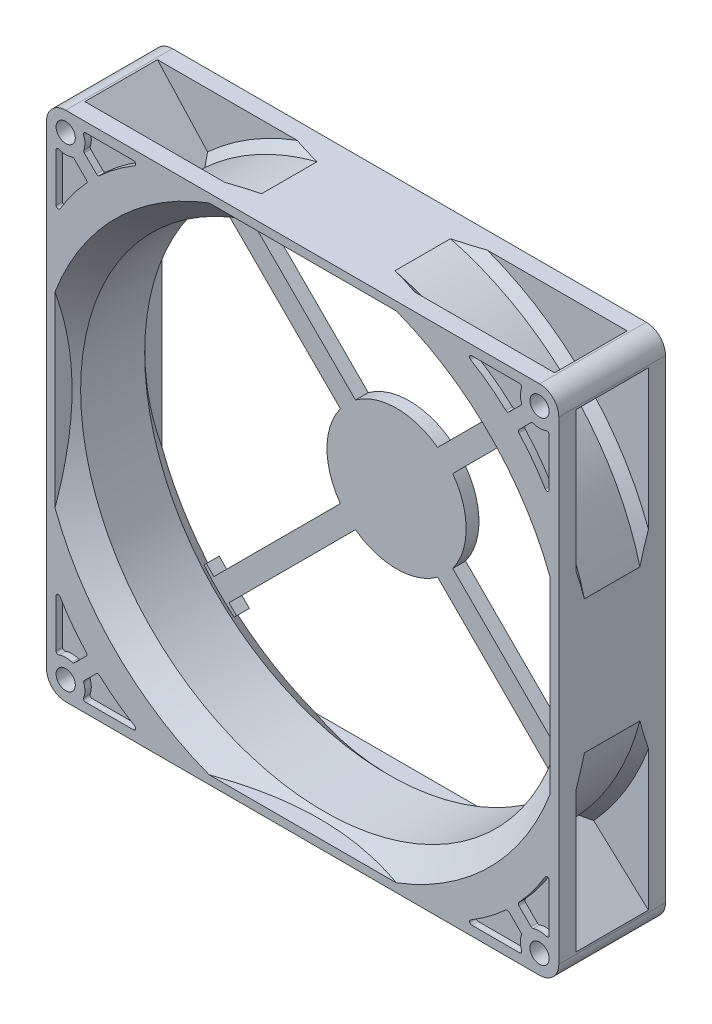
SolidWorks part; units mm, degrees
ref_plane "Front Plane" through (0, 0, 0) normal (0, 0, 1) x (1, 0, 0)
ref_plane "Top Plane" through (0, 0, 0) normal (0, 1, 0) x (1, 0, 0)
ref_plane "Right Plane" through (0, 0, 0) normal (1, 0, 0) x (0, 0, -1)
sketch "Sketch1" plane through (0, 0, 0) normal (0, 0, 1) x (1, 0, 0)
  line L1 (-55.5, -60) -> (55.5, -60)
  line L2 (-60, -55.5) -> (-60, 55.5)
  line L3 (-55.5, 60) -> (55.5, 60)
  line L4 (60, -55.5) -> (60, 55.5)
  line L5 (-60, -60) -> (60, 60) construction
  line L6 (-60, 60) -> (60, -60) construction
  arc A0 (-55.5, -60) -> (-60, -55.5) centre (-55.5, -55.5) cw
  arc A1 (55.5, -60) -> (60, -55.5) centre (55.5, -55.5) ccw
  arc A2 (55.5, 60) -> (60, 55.5) centre (55.5, 55.5) cw
  arc A3 (-60, 55.5) -> (-55.5, 60) centre (-55.5, 55.5) cw
  circle A4 centre (-55.5, 55.5) radius 2.25
  circle A5 centre (-55.5, -55.5) radius 2.25
  circle A6 centre (55.5, -55.5) radius 2.25
  circle A7 centre (55.5, 55.5) radius 2.25
  point P0 (0, 0)
  dimension "D3" = 4.5
  dimension "D4" = 4.5
  dimension "D1" = 120
  dimension "D2" = 120
  dimension "D5" = 4.5
extrude "Boss-Extrude1" add sketch "Sketch1" along normal mid plane 25
sketch "Sketch3" plane through (0, 0, 12.5) normal (0, 0, 1) x (1, 0, 0)
  line L0 (-39.6029, -57.75) -> (-50.8163, -57.75)
  line L1 (-48.3027, -50.6714) -> (-51.1323, -53.5)
  line L2 (-60, 0) -> (60, 0) construction
  line L3 (-60, 55.5) -> (-60, -55.5) construction
  line L4 (60, -55.5) -> (60, 55.5) construction
  line L5 (0, 60) -> (0, -60) construction
  line L6 (55.5, 60) -> (-55.5, 60) construction
  line L7 (-55.5, -60) -> (55.5, -60) construction
  line L8 (-48.3027, 50.6714) -> (-51.1323, 53.5)
  line L9 (-39.6029, 57.75) -> (-50.8163, 57.75)
  line L10 (39.6029, 57.75) -> (50.8163, 57.75)
  line L11 (48.3027, 50.6714) -> (51.1323, 53.5)
  line L12 (48.3027, -50.6714) -> (51.1323, -53.5)
  line L13 (39.6029, -57.75) -> (50.8163, -57.75)
  line L14 (-58.682, 58.682) -> (58.682, -58.682) construction
  line L15 (58.682, 58.682) -> (-58.682, -58.682) construction
  line L16 (-50.6714, -48.3027) -> (-53.5, -51.1323)
  line L17 (-57.75, -39.6029) -> (-57.75, -50.8163)
  line L18 (-50.6714, 48.3027) -> (-53.5, 51.1323)
  line L19 (-57.75, 39.6029) -> (-57.75, 50.8163)
  line L20 (57.75, 39.6029) -> (57.75, 50.8163)
  line L21 (50.6714, 48.3027) -> (53.5, 51.1323)
  line L22 (57.75, -39.6029) -> (57.75, -50.8163)
  line L23 (50.6714, -48.3027) -> (53.5, -51.1323)
  arc A0 (-51.2846, -57.075) -> (-51.2509, -54.0183) centre (-55.5, -55.5) ccw
  arc A1 (-39.6029, -57.75) -> (-39.3478, -56.82) centre (-39.6029, -57.25) ccw
  arc A2 (-39.3478, -56.82) -> (-47.6098, -50.6579) centre (-14.3459, -14.6785) cw
  arc A3 (-47.6098, -50.6579) -> (-48.3027, -50.6714) centre (-47.9492, -51.025) ccw
  arc A4 (-50.8163, -57.75) -> (-51.2846, -57.075) centre (-50.8163, -57.25) cw
  arc A5 (-51.1323, -53.5) -> (-51.2509, -54.0183) centre (-50.7788, -53.8536) ccw
  circle A6 centre (-55.5, -55.5) radius 2.25 construction
  arc A7 (-51.1323, 53.5) -> (-51.2509, 54.0183) centre (-50.7788, 53.8536) cw
  arc A8 (-50.8163, 57.75) -> (-51.2846, 57.075) centre (-50.8163, 57.25) ccw
  arc A9 (-47.6098, 50.6579) -> (-48.3027, 50.6714) centre (-47.9492, 51.025) cw
  arc A10 (-39.3478, 56.82) -> (-47.6098, 50.6579) centre (-14.3459, 14.6785) ccw
  arc A11 (-39.6029, 57.75) -> (-39.3478, 56.82) centre (-39.6029, 57.25) cw
  arc A12 (-51.2846, 57.075) -> (-51.2509, 54.0183) centre (-55.5, 55.5) cw
  arc A13 (51.2846, 57.075) -> (51.2509, 54.0183) centre (55.5, 55.5) ccw
  arc A14 (39.6029, 57.75) -> (39.3478, 56.82) centre (39.6029, 57.25) ccw
  arc A15 (39.3478, 56.82) -> (47.6098, 50.6579) centre (14.3459, 14.6785) cw
  arc A16 (47.6098, 50.6579) -> (48.3027, 50.6714) centre (47.9492, 51.025) ccw
  arc A17 (50.8163, 57.75) -> (51.2846, 57.075) centre (50.8163, 57.25) cw
  arc A18 (51.1323, 53.5) -> (51.2509, 54.0183) centre (50.7788, 53.8536) ccw
  arc A19 (51.1323, -53.5) -> (51.2509, -54.0183) centre (50.7788, -53.8536) cw
  arc A20 (50.8163, -57.75) -> (51.2846, -57.075) centre (50.8163, -57.25) ccw
  arc A21 (47.6098, -50.6579) -> (48.3027, -50.6714) centre (47.9492, -51.025) cw
  arc A22 (39.3478, -56.82) -> (47.6098, -50.6579) centre (14.3459, -14.6785) ccw
  arc A23 (39.6029, -57.75) -> (39.3478, -56.82) centre (39.6029, -57.25) cw
  arc A24 (51.2846, -57.075) -> (51.2509, -54.0183) centre (55.5, -55.5) cw
  arc A25 (-55.5, 60) -> (-60, 55.5) centre (-55.5, 55.5) ccw construction
  arc A26 (55.5, -60) -> (60, -55.5) centre (55.5, -55.5) ccw construction
  arc A27 (60, 55.5) -> (55.5, 60) centre (55.5, 55.5) ccw construction
  arc A28 (-60, -55.5) -> (-55.5, -60) centre (-55.5, -55.5) ccw construction
  arc A29 (-53.5, -51.1323) -> (-54.0183, -51.2509) centre (-53.8536, -50.7788) cw
  arc A30 (-57.75, -50.8163) -> (-57.075, -51.2846) centre (-57.25, -50.8163) ccw
  arc A31 (-57.075, -51.2846) -> (-54.0183, -51.2509) centre (-55.5, -55.5) cw
  arc A32 (-50.6579, -47.6098) -> (-50.6714, -48.3027) centre (-51.025, -47.9492) cw
  arc A33 (-56.82, -39.3478) -> (-50.6579, -47.6098) centre (-14.6785, -14.3459) ccw
  arc A34 (-57.75, -39.6029) -> (-56.82, -39.3478) centre (-57.25, -39.6029) cw
  arc A35 (-57.075, 51.2846) -> (-54.0183, 51.2509) centre (-55.5, 55.5) ccw
  arc A36 (-57.75, 50.8163) -> (-57.075, 51.2846) centre (-57.25, 50.8163) cw
  arc A37 (-53.5, 51.1323) -> (-54.0183, 51.2509) centre (-53.8536, 50.7788) ccw
  arc A38 (-50.6579, 47.6098) -> (-50.6714, 48.3027) centre (-51.025, 47.9492) ccw
  arc A39 (-57.75, 39.6029) -> (-56.82, 39.3478) centre (-57.25, 39.6029) ccw
  arc A40 (-56.82, 39.3478) -> (-50.6579, 47.6098) centre (-14.6785, 14.3459) cw
  arc A41 (57.75, 39.6029) -> (56.82, 39.3478) centre (57.25, 39.6029) cw
  arc A42 (57.75, 50.8163) -> (57.075, 51.2846) centre (57.25, 50.8163) ccw
  arc A43 (50.6579, 47.6098) -> (50.6714, 48.3027) centre (51.025, 47.9492) cw
  arc A44 (56.82, 39.3478) -> (50.6579, 47.6098) centre (14.6785, 14.3459) ccw
  arc A45 (53.5, 51.1323) -> (54.0183, 51.2509) centre (53.8536, 50.7788) cw
  arc A46 (57.075, 51.2846) -> (54.0183, 51.2509) centre (55.5, 55.5) cw
  arc A47 (57.75, -39.6029) -> (56.82, -39.3478) centre (57.25, -39.6029) ccw
  arc A48 (56.82, -39.3478) -> (50.6579, -47.6098) centre (14.6785, -14.3459) cw
  arc A49 (50.6579, -47.6098) -> (50.6714, -48.3027) centre (51.025, -47.9492) ccw
  arc A50 (57.075, -51.2846) -> (54.0183, -51.2509) centre (55.5, -55.5) ccw
  arc A51 (57.75, -50.8163) -> (57.075, -51.2846) centre (57.25, -50.8163) cw
  arc A52 (53.5, -51.1323) -> (54.0183, -51.2509) centre (53.8536, -50.7788) ccw
  point P14 (-51.6029, -57.75)
  point P44 (-51.6029, 57.75)
  point P59 (51.6029, 57.75)
  point P74 (51.6029, -57.75)
  point P97 (-57.75, -51.6029)
  point P111 (-57.75, 51.6029)
  point P125 (57.75, 51.6029)
  point P146 (57.75, -51.6029)
  dimension "D1" = 9
  dimension "D2" = 49
  dimension "D3" = 0.5
  dimension "D5" = 0.5
  dimension "D6" = 0.5
  dimension "D4" = 12
  dimension "D7" = 4.001
  dimension "D8" = 4.25
  dimension "D9" = 2.475
extrude "Cut-Extrude1" cut sketch "Sketch3" against normal blind 1.5
mirror "Mirror1" about plane through (0, 0, 0) normal (0, 0, 1) of "Cut-Extrude1"
sketch "Sketch5" plane through (0, 0, 12.5) normal (0, 0, 1) x (1, 0, 0)
  line L0 (55.5, 60) -> (-55.5, 60) construction
  line L1 (-58, -58) -> (58, -58)
  line L2 (-58, -58) -> (-58, 58)
  line L3 (-58, 58) -> (58, 58)
  line L4 (58, -58) -> (58, 58)
  line L5 (-58, -58) -> (58, 58) construction
  line L6 (-58, 58) -> (58, -58) construction
  line L7 (60, -55.5) -> (60, 55.5) construction
  point P0 (0, 0)
  dimension "D1" = 2
  dimension "D2" = 2
split "Split1" trim tools "Sketch5" bodies to split 103 resulting bodies 104 105
sketch "Sketch6" plane through (0, 0, 12.5) normal (0, 0, 1) x (1, 0, 0)
  circle A0 centre (0, 0) radius 57
  dimension "D1" = 114
extrude "Cut-Extrude2" cut sketch "Sketch6" against normal blind 25
chamfer "Chamfer1" distance 5 angle 45 2 edges at (57, 0, -12.5) (57, 0, 12.5)
sketch "Sketch7" plane through (0, 0, -12.5) normal (0, 0, -1) x (-1, 0, 0)
  line L0 (0, 60) -> (0, -60) construction
  line L1 (-55.5, 60) -> (55.5, 60) construction
  line L2 (55.5, -60) -> (-55.5, -60) construction
  line L3 (-60, 0) -> (60, 0) construction
  line L4 (-60, -55.5) -> (-60, 55.5) construction
  line L5 (60, 55.5) -> (60, -55.5) construction
  circle A0 centre (-55.5, 55.5) radius 3.4
  circle A1 centre (-55.5, -55.5) radius 3.4
  circle A2 centre (55.5, 55.5) radius 3.4
  circle A3 centre (55.5, -55.5) radius 3.4
  dimension "D1" = 6.8
extrude "Cut-Extrude3" cut sketch "Sketch7" against normal blind 2.5
combine bodies "Combine1" operation type add bodies to combine 108 107
sketch "Sketch8" plane through (0, 0, -12.5) normal (0, 0, -1) x (-1, 0, 0)
  line L0 (-58.682, 58.682) -> (58.682, -58.682) construction
  line L1 (58.682, 58.682) -> (-58.682, -58.682) construction
  line L2 (-42.7786, 39.2431) -> (-13.1572, 9.6217)
  line L3 (-9.6217, 13.1572) -> (-39.2431, 42.7786)
  line L4 (-47.2334, 40.1623) -> (-44.5464, 37.4753)
  line L5 (-44.5464, 37.4753) -> (-42.7786, 39.2431)
  line L6 (-37.4753, 44.5464) -> (-40.1623, 47.2334)
  line L7 (-39.2431, 42.7786) -> (-37.4753, 44.5464)
  line L8 (13.1572, 9.6217) -> (42.7786, 39.2431)
  line L9 (39.2431, 42.7786) -> (9.6217, 13.1572)
  line L10 (37.4753, 44.5464) -> (39.2431, 42.7786)
  line L11 (40.1623, 47.2334) -> (37.4753, 44.5464)
  line L12 (44.5464, 37.4753) -> (47.2334, 40.1623)
  line L13 (42.7786, 39.2431) -> (44.5464, 37.4753)
  line L14 (9.6217, -13.1572) -> (39.2431, -42.7786)
  line L15 (42.7786, -39.2431) -> (13.1572, -9.6217)
  line L16 (44.5464, -37.4753) -> (42.7786, -39.2431)
  line L17 (47.2334, -40.1623) -> (44.5464, -37.4753)
  line L18 (37.4753, -44.5464) -> (40.1623, -47.2334)
  line L19 (39.2431, -42.7786) -> (37.4753, -44.5464)
  line L20 (-13.1572, -9.6217) -> (-42.7786, -39.2431)
  line L21 (-39.2431, -42.7786) -> (-9.6217, -13.1572)
  line L22 (-37.4753, -44.5464) -> (-39.2431, -42.7786)
  line L23 (-40.1623, -47.2334) -> (-37.4753, -44.5464)
  line L24 (-44.5464, -37.4753) -> (-47.2334, -40.1623)
  line L25 (-42.7786, -39.2431) -> (-44.5464, -37.4753)
  arc A0 (-13.1572, 9.6217) -> (-13.1572, -9.6217) centre (0, 0) ccw
  arc A1 (-55.5, 60) -> (-60, 55.5) centre (-55.5, 55.5) ccw construction
  arc A2 (55.5, -60) -> (60, -55.5) centre (55.5, -55.5) ccw construction
  arc A3 (60, 55.5) -> (55.5, 60) centre (55.5, 55.5) ccw construction
  arc A4 (-60, -55.5) -> (-55.5, -60) centre (-55.5, -55.5) ccw construction
  arc A5 (-21.9089, 58) -> (-58, 21.9089) centre (0, 0) ccw construction
  arc A6 (-40.1623, 47.2334) -> (-47.2334, 40.1623) centre (0, 0) ccw
  arc A7 (47.2334, 40.1623) -> (40.1623, 47.2334) centre (0, 0) ccw
  arc A8 (40.1623, -47.2334) -> (47.2334, -40.1623) centre (0, 0) ccw
  arc A9 (-47.2334, -40.1623) -> (-40.1623, -47.2334) centre (0, 0) ccw
  arc A10 (9.6217, 13.1572) -> (-9.6217, 13.1572) centre (0, 0) ccw
  arc A11 (13.1572, -9.6217) -> (13.1572, 9.6217) centre (0, 0) ccw
  arc A12 (-9.6217, -13.1572) -> (9.6217, -13.1572) centre (0, 0) ccw
  point P55 (0, 0)
  dimension "D1" = 32.6
  dimension "D2" = 2.5
  dimension "D3" = 2.5
  dimension "D4" = 3.8
  dimension "D5" = 5
  dimension "D6" = 4
extrude "Boss-Extrude2" add sketch "Sketch8" against normal blind 3 separate body
sketch "Sketch10" plane through (0, 0, 0) normal (0, 0, 1) x (1, 0, 0)
  line L0 (41.9004, -45.6986) -> (55.0132, -60)
  line L1 (-55.5, -60) -> (55.5, -60) construction
  line L2 (15.6205, -60) -> (55.0132, -60)
  line L3 (0, 0) -> (0, -60) construction
  line L4 (-55.5, -60) -> (55.5, -60) construction
  line L5 (-15.6205, -60) -> (-55.0132, -60)
  line L6 (-41.9004, -45.6986) -> (-55.0132, -60)
  arc A0 (21.9089, -58) -> (58, -21.9089) centre (0, 0) ccw construction
  arc A1 (15.6205, -60) -> (41.9004, -45.6986) centre (0, 0) ccw
  circle A2 centre (55.5, -55.5) radius 3.4 construction
  arc A3 (-15.6205, -60) -> (-41.9004, -45.6986) centre (0, 0) cw
extrude "Cut-Extrude4" cut sketch "Sketch10" against normal mid plane 17
chamfer "Chamfer2" distance 2 angle 45 4 edges at (29.636, -54.4583, -8.5) (29.636, -54.4583, 8.5) (-29.636, -54.4583, 8.5) (-29.636, -54.4583, -8.5)
pattern_circular "CirPattern1" count 4 over 360 about axis through (0, 0, 7.5) along (0, 0, 1) of "Chamfer2", "Cut-Extrude4"
combine bodies "Combine2" operation type add bodies to combine 113 111
